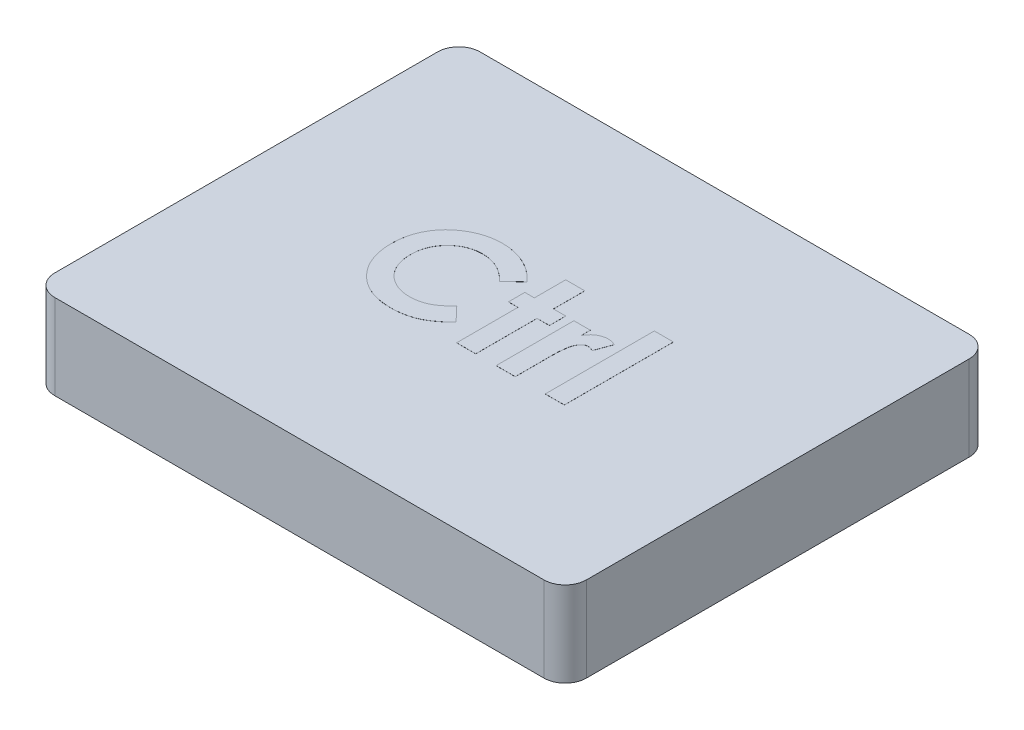
SolidWorks part; units mm, degrees
ref_plane "Front Plane" through (0, 0, 0) normal (0, 0, 1) x (1, 0, 0)
ref_plane "Top Plane" through (0, 0, 0) normal (0, 1, 0) x (1, 0, 0)
ref_plane "Right Plane" through (0, 0, 0) normal (1, 0, 0) x (0, 0, -1)
sketch "Sketch1" plane through (0, 0, 0) normal (0, 1, 0) x (1, 0, 0)
  line L0 (0, 0) -> (15.875, 0)
  line L1 (15.875, 0) -> (15.875, 12.7)
  line L2 (15.875, 12.7) -> (0, 12.7)
  line L3 (0, 12.7) -> (0, 0)
  dimension "D1" = 15.875
  dimension "D2" = 12.7
extrude "Boss-Extrude1" add sketch "Sketch1" along normal blind 2.54
fillet "Fillet1" radius 0.635 4 edges at (0, 1.27, -12.7) (15.875, 1.27, -12.7) (15.875, 1.27, 0) (0, 1.27, 0)
shell "Shell1" thickness 0.635 removed face at (7.9375, 0, -6.35)
sketch "Sketch2" plane through (0, 1.905, 0) normal (0, -1, 0) x (-1, 0, 0)
  line L0 (-0.635, 6.35) -> (-15.24, 6.35) construction
  line L1 (-0.635, 12.065) -> (-0.635, 0.635) construction
  line L2 (-15.24, 0.635) -> (-15.24, 12.065) construction
  line L3 (-7.9375, 0.635) -> (-7.9375, 12.065) construction
  line L4 (-0.635, 0.635) -> (-15.24, 0.635) construction
  line L5 (-15.24, 12.065) -> (-0.635, 12.065) construction
  circle A0 centre (-7.9375, 6.35) radius 2.54
  dimension "D1" = 5.08
extrude "Boss-Extrude2" add sketch "Sketch2" along normal up to surface (1.905 mm away) up to face at (7.9375, 0, -6.35)
sketch "Sketch3" plane through (0, 2.54, 0) normal (0, 1, 0) x (1, 0, 0)
  line L0 (0, 12.065) -> (0, 0.635) construction
  line L1 (15.24, 12.7) -> (0.635, 12.7) construction
  text T0 "<b>Ctrl</b>"
  dimension "D1" = 4.064
  dimension "D2" = 7.874
extrude "Boss-Extrude3" add sketch "Sketch3" along normal blind 0.0025
